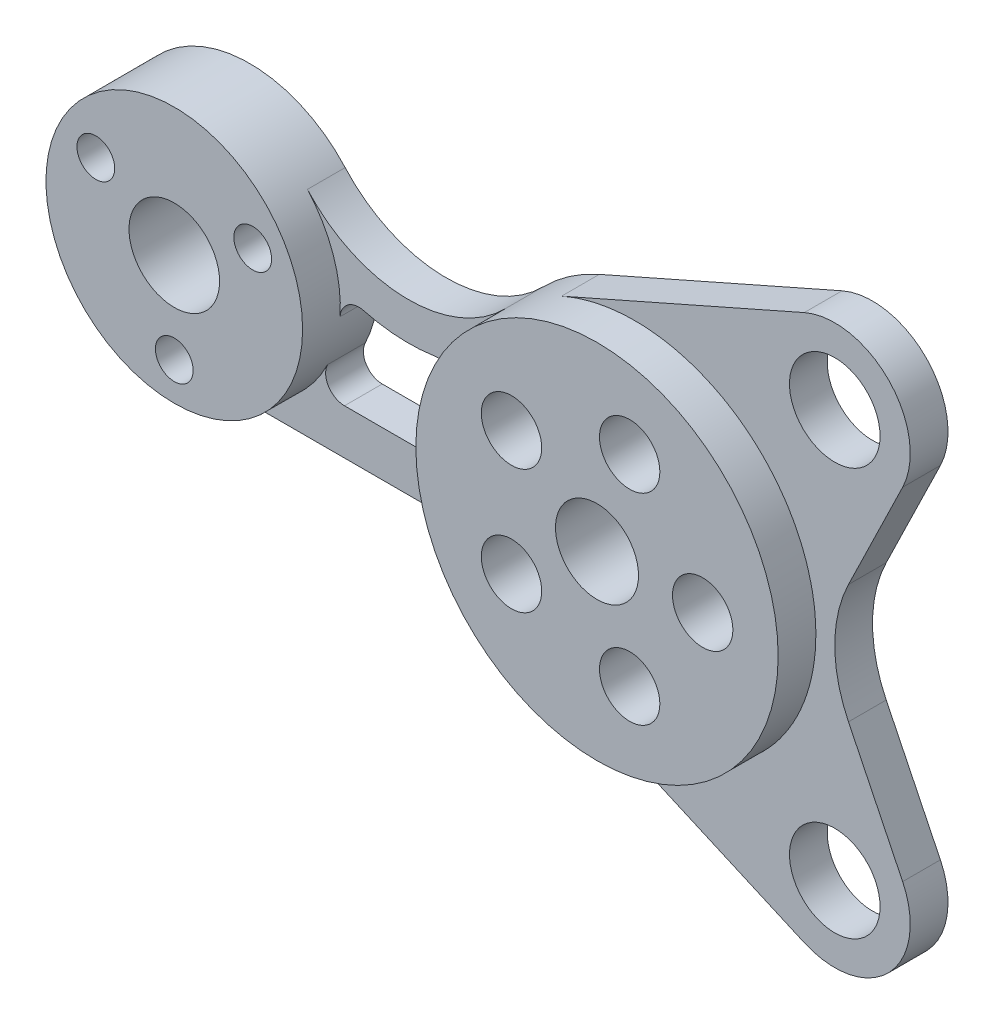
SolidWorks part; units mm, degrees
note: The reader was unsure of these and kept them because the rebuilt part matched: shared geometry of "Эскиз1<3>".
ref_plane "Спереди" through (0, 0, 0) normal (0, 0, 1) x (1, 0, 0)
ref_plane "Сверху" through (0, 0, 0) normal (0, 1, 0) x (1, 0, 0)
ref_plane "Справа" through (0, 0, 0) normal (1, 0, 0) x (0, 0, -1)
sketch "Эскиз1" plane through (0, 0, 0) normal (0, 0, 1) x (1, 0, 0)
  line L0 (0, 0) -> (0, 98.9916) construction
  line L1 (0, 0) -> (0, -82.7343) construction
  line L2 (-112, -22) -> (-50.9902, -22)
  line L3 (-19.3826, -43.9126) -> (44.9239, -72.2969)
  line L4 (0, 0) -> (53, 0) construction
  line L5 (56.6296, -15.7531) -> (70.9835, -45.2483)
  line L6 (-76.9001, -10) -> (-52.7636, -10)
  line L7 (44.9239, 72.2969) -> (-19.3826, 43.9126)
  line L8 (56.6296, 15.7531) -> (70.9835, 45.2483)
  line L9 (48, 0) -> (56.6296, 15.7531) construction
  line L10 (-112, 12) -> (-112, -22) construction
  line L11 (48, 0) -> (56.6296, -15.7531) construction
  line L12 (53, 54) -> (53, -54) construction
  line L13 (8.6525, 26.6296) -> (0, 0) construction
  circle A0 centre (0, 0) radius 48
  circle A1 centre (-22.6525, 16.458) radius 8
  circle A2 centre (8.6525, 26.6296) radius 8
  circle A3 centre (28, 0) radius 8
  circle A4 centre (8.6525, -26.6296) radius 8
  circle A5 centre (-22.6525, -16.458) radius 8
  circle A7 centre (0, 0) radius 11
  circle A8 centre (53, 54) radius 12
  circle A9 centre (-112, 12) radius 34
  circle A10 centre (53, -54) radius 12
  arc A11 (-86.726, 34.7426) -> (-34.2659, 33.6132) centre (-59.9654, 58.8231) ccw
  arc A12 (70.9835, 45.2483) -> (44.9239, 72.2969) centre (53, 54) ccw
  arc A13 (44.9239, -72.2969) -> (70.9835, -45.2483) centre (53, -54) ccw
  circle A14 centre (-112, 12) radius 12
  arc A15 (-38.8497, -28.1905) -> (-50.9902, -22) centre (-50.9902, -37) ccw
  arc A16 (-71.7923, 14.3694) -> (-78.0678, 9.8532) centre (-73.0778, 9.5375) ccw
  arc A17 (-47.3936, 7.6055) -> (-53.079, 13.3414) centre (-52.3305, 8.3978) ccw
  arc A18 (-81.4001, -2.8205) -> (-76.9001, -10) centre (-76.9001, -5) ccw
  arc A19 (-52.7636, -10) -> (-47.7859, -4.5283) centre (-52.7636, -5) ccw
  arc A20 (-71.7923, 14.3694) -> (-53.079, 13.3414) centre (-59.9654, 58.8231) ccw
  arc A21 (56.6296, 15.7531) -> (56.6296, -15.7531) centre (89, 0) ccw
  circle A22 centre (-132.7846, 24) radius 5
  circle A23 centre (-91.2154, 24) radius 5
  circle A24 centre (-112, -12) radius 5
  point P19 (0, 0)
  point P62 (0, 0)
  point P67 (-112, 12)
  dimension "D1" = 96
  dimension "D5" = 22
  dimension "D6" = 53
  dimension "D9" = 36
  dimension "D7" = 24
  dimension "D8" = 68
  dimension "D11" = 40
  dimension "D12" = 20
  dimension "D13" = 24
  dimension "D15" = 12
  dimension "D14" = 15
  dimension "D17" = 5
  dimension "D18" = 5
  dimension "D19" = 5
  dimension "D20" = 5
  dimension "D22" = 10
  dimension "D24" = 72
  dimension "D25" = 24
  dimension "D27" = 10
  dimension "D4" = 16
  dimension "D29" = 5
  dimension "D31" = 28
  dimension "D10" = 108
  dimension "D16" = 112
  dimension "D21" = 12
  dimension "D23" = 54
  dimension "D26" = 36
  dimension "D30" = 24
  dimension "D32" = 18
  dimension "D28" = 3
extrude "Бобышка-Вытянуть1" add sketch "Эскиз1" along normal blind 10 contours A16 A20 A17 A0 A11 A9 | A19 L6 A18 A9 L2 A15 A0 | A21 L8 A12 L7 A0 L3 A13 L5 A8 A10
extrude "Бобышка-Вытянуть2" add sketch "Эскиз1<3>" along normal blind 20 contours A9 A24 A23 A22 A14 | A0 A7 A5 A4 A3 A2 A1
sketch "Эскиз1<3>" plane through (0, 0, 0) normal (0, 0, 1) x (1, 0, 0) same geometry as "Эскиз1"
